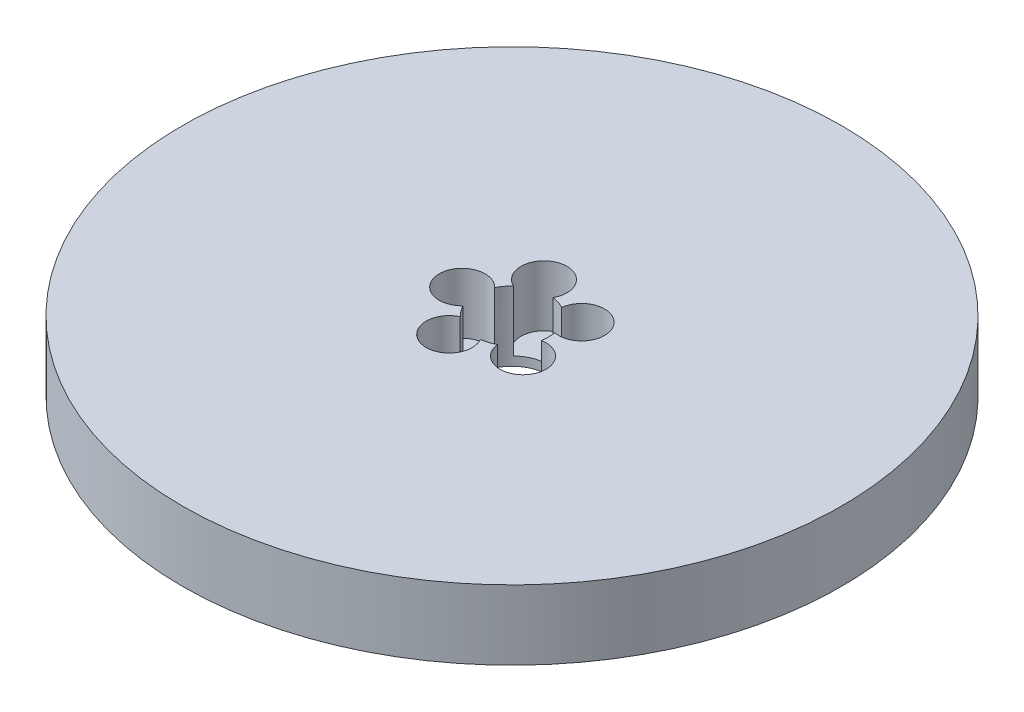
SolidWorks part; units mm, degrees
ref_plane "Front Plane" through (0, 0, 0) normal (0, 0, 1) x (1, 0, 0)
ref_plane "Top Plane" through (0, 0, 0) normal (0, 1, 0) x (1, 0, 0)
ref_plane "Right Plane" through (0, 0, 0) normal (1, 0, 0) x (0, 0, -1)
sketch "Sketch1" plane through (0, 0, 0) normal (0, 1, 0) x (1, 0, 0)
  circle A0 centre (0, 0) radius 90
  dimension "FLANGE_OD" = 180
extrude "Boss-Extrude1" add sketch "Sketch1" along normal blind 19
sketch "Sketch2" plane through (0, 0, 0) normal (0, 1, 0) x (1, 0, 0)
  circle A0 centre (0, 0) radius 10
  dimension "BORE_D" = 20
extrude "Cut-Extrude1" cut sketch "Sketch2" along normal through all
sketch "Sketch3" plane through (0, 19, 0) normal (0, 1, 0) x (1, 0, 0)
  circle A0 centre (0, 0) radius 13.6127 construction
  circle A1 centre (-13.6127, 0) radius 6.2772
  dimension "BOLT_D" = 12.5544
  dimension "BOLT_PCD" = 27.2254
extrude "Cut-Extrude2" cut sketch "Sketch3" against normal blind 16.5497
pattern_circular "CirPattern1" count 5 over 360 about axis through (0, 0, 0) along (0, 1, 0) of "Cut-Extrude2"
